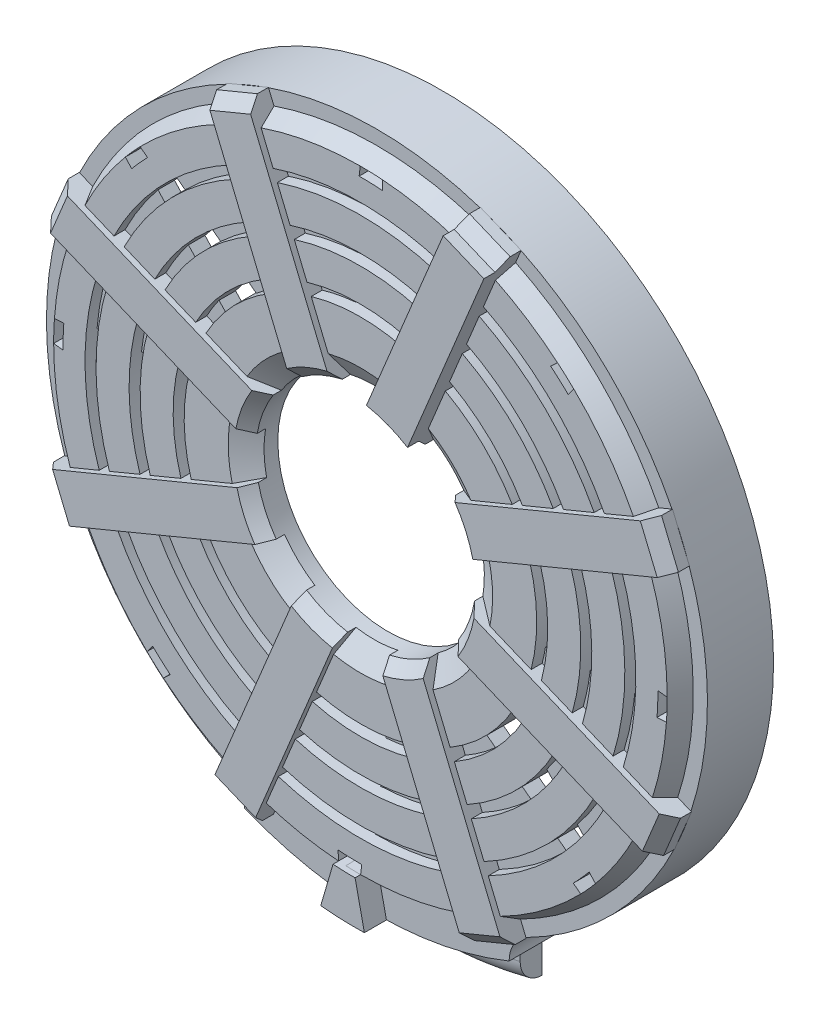
SolidWorks part; units mm, degrees
material "AISI 304"
ref_plane "Front Plane" through (0, 0, 0) normal (0, 0, 1) x (1, 0, 0)
ref_plane "Top Plane" through (0, 0, 0) normal (0, 1, 0) x (1, 0, 0)
ref_plane "Right Plane" through (0, 0, 0) normal (1, 0, 0) x (0, 0, -1)
sketch "草图2" plane through (0, 0, 20) normal (0, 0, 1) x (1, 0, 0)
  line L2 (12, -35.4955) -> (12, -29.3939)
  line L3 (-12, -29.3939) -> (-12, -35.4955)
  circle A1 centre (0, 0) radius 26.9356
  arc A2 (13.6364, -26.7217) -> (-13.6364, -26.7217) centre (0, 0) ccw
  arc A5 (13.6364, -26.7217) -> (12, -29.3939) centre (15, -29.3939) ccw
  arc A6 (-12, -35.4955) -> (12, -35.4955) centre (0, 0) ccw
  arc A7 (-12, -29.3939) -> (-13.6364, -26.7217) centre (-15, -29.3939) ccw
extrude "凸台-拉伸1" add sketch "草图2" along normal blind 2
sketch "草图3" plane through (0, 0, 22) normal (0, 0, 1) x (1, 0, 0)
  line L0 (-9, -36.3721) -> (-9, -28.6182)
  line L1 (0, -37.469) -> (0, -24.2396) construction
  line L2 (9, -36.3721) -> (9, -28.6182)
  line L3 (12, -35.4955) -> (12, -29.3939) construction
  line L4 (-12, -29.3939) -> (-12, -35.4955) construction
  line L5 (12, -35.4955) -> (12, -29.3939)
  line L6 (-12, -29.3939) -> (-12, -35.4955)
  arc A0 (-12, -35.4955) -> (12, -35.4955) centre (0, 0) ccw construction
  circle A1 centre (0, 0) radius 30 construction
  arc A2 (-13.6364, -26.7217) -> (-9, -28.6182) centre (0, 0) ccw
  arc A4 (13.6364, -26.7217) -> (12, -29.3939) centre (15, -29.3939) ccw construction
  arc A5 (-12, -29.3939) -> (-13.6364, -26.7217) centre (-15, -29.3939) ccw construction
  arc A6 (13.6364, -26.7217) -> (12, -29.3939) centre (15, -29.3939) ccw
  arc A7 (-12, -35.4955) -> (-9, -36.3721) centre (0, 0) ccw
  arc A8 (-12, -29.3939) -> (-13.6364, -26.7217) centre (-15, -29.3939) ccw
  arc A9 (9, -28.6182) -> (13.6364, -26.7217) centre (0, 0) ccw
  arc A10 (9, -36.3721) -> (12, -35.4955) centre (0, 0) ccw
  dimension "D1" = 9
extrude "切除-拉伸3" cut sketch "草图3" against normal blind 2
sketch "草图4" plane through (0, 0, 22) normal (0, 0, 1) x (1, 0, 0)
  line L0 (9, -28.6182) -> (9, -36.3721) construction
  line L1 (-9, -36.3721) -> (-9, -28.6182) construction
  line L6 (9, -35) -> (9, -36.3721)
  line L7 (-9, -36.3721) -> (-9, -35)
  arc A0 (-9, -36.3721) -> (9, -36.3721) centre (0, 0) ccw construction
  arc A1 (-9, -36.3721) -> (9, -36.3721) centre (0, 0) ccw
  arc A5 (-9, -35) -> (9, -35) centre (0, 0) ccw
extrude "切除-拉伸4" cut sketch "草图4" against normal blind 2
fillet "圆角2" radius 2 1 edges at (0, -36.1386, 22)
sketch "草图7" plane through (0, 0, 22) normal (0, 0, 1) x (1, 0, 0)
  line L2 (-9, -28.6182) -> (-9, -32.9309)
  line L3 (9, -32.9309) -> (9, -28.6182)
  line L4 (-9, -30.4467) -> (-9, -32.9309)
  line L5 (9, -32.9309) -> (9, -30.4467)
  arc A0 (-12, -29.3939) -> (-13.6364, -26.7217) centre (-15, -29.3939) ccw construction
  arc A2 (-9, -32.9309) -> (9, -32.9309) centre (0, 0) ccw
  arc A3 (9, -28.6182) -> (-9, -28.6182) centre (0, 0) ccw
  arc A4 (-9, -32.9309) -> (9, -32.9309) centre (0, 0) ccw
  arc A5 (9, -28.6182) -> (13.6364, -26.7217) centre (0, 0) ccw
  arc A6 (13.6364, -26.7217) -> (12, -29.3939) centre (15, -29.3939) ccw construction
  arc A7 (13.6364, -26.7217) -> (12, -29.3939) centre (15, -29.3939) ccw
  arc A8 (9, -28.6182) -> (-9, -28.6182) centre (0, 0) ccw construction
  arc A9 (9, -28.6182) -> (13.6364, -26.7217) centre (0, 0) ccw
  arc A10 (13.6364, -26.7217) -> (12, -29.3939) centre (15, -29.3939) ccw
  arc A11 (-12, -29.3939) -> (-13.6364, -26.7217) centre (-15, -29.3939) ccw
  arc A12 (-12, -29.3939) -> (12, -29.3939) centre (0, 0) ccw
  arc A13 (-13.6364, -26.7217) -> (13.6364, -26.7217) centre (0, 0) ccw
  arc A14 (-13.6364, -26.7217) -> (-9, -28.6182) centre (0, 0) ccw
  arc A15 (-13.6364, -26.7217) -> (-9, -28.6182) centre (0, 0) ccw
  line M7 (-9, -28.6182) -> (-9, -32.9309)
  line M9 (9, -32.9309) -> (9, -28.6182)
  arc M10 (9, -28.6182) -> (-9, -28.6182) centre (0, 0) ccw
  dimension "D1" = 0
extrude "凸台-拉伸2" add sketch "草图7" against normal blind 2 contours A11 A12 M7 M10 | A13 A12 M7 M9 | A12 A7 M9 M10 region at (0, -30.4259, 22) region at (-10.6878, -28.8911, 22) region at (10.6878, -28.8911, 22)
sketch "草图8" plane through (0, 0, 22) normal (0, 0, 1) x (1, 0, 0)
  arc A0 (-12, -29.3939) -> (12, -29.3939) centre (0, 0) ccw
  arc A1 (13.6364, -26.7217) -> (12, -29.3939) centre (15, -29.3939) ccw construction
  circle A2 centre (0, 0) radius 30 construction
  arc A3 (-12, -29.3939) -> (-13.6364, -26.7217) centre (-15, -29.3939) ccw construction
  arc A4 (13.6364, -26.7217) -> (12, -29.3939) centre (15, -29.3939) ccw
  arc A5 (-13.6364, -26.7217) -> (13.6364, -26.7217) centre (0, 0) ccw
  arc A6 (-12, -29.3939) -> (-13.6364, -26.7217) centre (-15, -29.3939) ccw
extrude "凸台-拉伸3" add sketch "草图8" along normal blind 4
sketch "草图9" plane through (0, 0, 22) normal (0, 0, 1) x (1, 0, 0)
  circle A3 centre (0, 0) radius 27
  circle A4 centre (0, 0) radius 30
extrude "凸台-拉伸5" add sketch "草图9" along normal blind 4
sketch "草图10" plane through (0, 0, 26) normal (0, 0, 1) x (1, 0, 0)
  circle A0 centre (0, 0) radius 29
extrude "凸台-拉伸6" add sketch "草图10" along normal up to surface (1.5 mm away)
chamfer "倒角1" distance 2 angle 30 1 edges at (29, 0, 27.5) first distance on face at (29, 0, 26)
sketch "草图12" plane through (0, 0, 27.5) normal (0, 0, 1) x (1, 0, 0)
  circle A0 centre (0, 0) radius 10
extrude "切除-拉伸5" cut sketch "草图12" against normal blind 18
sketch "草图13" plane through (0, 0, 20) normal (0, 0, -1) x (-1, 0, 0)
  circle A0 centre (0, 0) radius 27
extrude "凸台-拉伸7" add sketch "草图13" against normal up to surface (6 mm away) up to face at (10, 0, 26)
sketch "草图14" plane through (0, 0, 27.5) normal (0, 0, 1) x (1, 0, 0)
  circle A0 centre (0, 0) radius 10
extrude "切除-拉伸6" cut sketch "草图14" against normal blind 8
sketch "草图16" plane through (0, 0, 20) normal (0, 0, -1) x (-1, 0, 0)
  circle A0 centre (0, 0) radius 27
extrude "切除-拉伸7" cut sketch "草图16" against normal blind 5
chamfer "倒角2" distance 2 angle 32 1 edges at (10, 0, 27.5) first distance on face at (10, 0, 27.5)
sketch "草图17" plane through (0, 0, 27.5) normal (0, 0, 1) x (1, 0, 0)
  circle A0 centre (0, 0) radius 25
  circle A1 centre (0, 0) radius 24
  circle A2 centre (0, 0) radius 21
  circle A3 centre (0, 0) radius 20
  circle A4 centre (0, 0) radius 17
  circle A5 centre (0, 0) radius 16
  dimension "D1" = 50
  dimension "D2" = 48
  dimension "D3" = 42
  dimension "D4" = 40
  dimension "D5" = 34
  dimension "D6" = 32
extrude "切除-拉伸10" cut sketch "草图17" against normal blind 1 contours A0 A1 | A2 A3 | A4 A5 region at (-24.2929, 0, 27.5) region at (-20.406, 0, 27.5) region at (-16.5192, 0, 27.5)
sketch "草图18" plane through (0, 0, 0) normal (0, 1, 0) x (1, 0, 0)
  line L0 (0, -20) -> (0, -40.9012) construction
  line L1 (-10.5, -23.7655) -> (-7.5, -23.7655)
  line L2 (-10.5, -23.7655) -> (-10.5, -22.7655)
  line L3 (-4.5, -23.7655) -> (-1.5, -23.7655)
  line L4 (-4.5, -23.7655) -> (-4.5, -22.7655)
  line L5 (-4.5, -22.7655) -> (-1.5, -22.7655)
  line L6 (-1.5, -23.7655) -> (-1.5, -22.7655)
  line L7 (-10.5, -22.7655) -> (-7.5, -22.7655)
  line L8 (-7.5, -23.7655) -> (-7.5, -22.7655)
  line L9 (7.5, -23.7655) -> (7.5, -22.7655)
  line L10 (10.5, -22.7655) -> (7.5, -22.7655)
  line L11 (1.5, -23.7655) -> (1.5, -22.7655)
  line L12 (4.5, -22.7655) -> (1.5, -22.7655)
  line L13 (4.5, -23.7655) -> (4.5, -22.7655)
  line L14 (4.5, -23.7655) -> (1.5, -23.7655)
  line L15 (10.5, -23.7655) -> (10.5, -22.7655)
  line L16 (10.5, -23.7655) -> (7.5, -23.7655)
  dimension "D1" = 1.5
  dimension "D2" = 2
extrude "切除-拉伸11" cut sketch "草图18" against normal blind 71
sketch "草图25" plane through (0, 0, 25) normal (0, 0, -1) x (-1, 0, 0)
  circle A0 centre (0, 0) radius 10.0206
  circle A1 centre (0, 0) radius 10.8
extrude "凸台-拉伸18" add sketch "草图25" against normal blind 1
sketch "草图26" plane through (0, 0, 27.5) normal (0, 0, 1) x (1, 0, 0)
  line L0 (0, 0.2463) -> (48.6925, 0.2463) construction
  line L1 (0, 0) -> (0, 32.9764) construction
  line L3 (8.1431, 5.8044) -> (26.8317, 13.5455)
  line L5 (9.7667, 2.1473) -> (28.3624, 9.8499)
  line L6 (26.8317, 13.5455) -> (28.3624, 9.8499)
  line L7 (9.8623, -1.6537) -> (28.551, -9.3948)
  line L8 (28.551, -9.3948) -> (27.0202, -13.0903)
  line L9 (8.4245, -5.3877) -> (27.0202, -13.0903)
  line L11 (5.8044, -8.1431) -> (13.5455, -26.8317)
  line L12 (13.5455, -26.8317) -> (9.8499, -28.3624)
  line L13 (2.1473, -9.7667) -> (9.8499, -28.3624)
  line L15 (-1.6537, -9.8623) -> (-9.3948, -28.551)
  line L16 (-9.3948, -28.551) -> (-13.0903, -27.0202)
  line L17 (-5.3877, -8.4245) -> (-13.0903, -27.0202)
  line L19 (-8.1431, -5.8044) -> (-26.8317, -13.5455)
  line L20 (-26.8317, -13.5455) -> (-28.3624, -9.8499)
  line L21 (-9.7667, -2.1473) -> (-28.3624, -9.8499)
  line L23 (-9.8623, 1.6537) -> (-28.551, 9.3948)
  line L24 (-28.551, 9.3948) -> (-27.0202, 13.0903)
  line L25 (-8.4245, 5.3877) -> (-27.0202, 13.0903)
  line L27 (-5.8044, 8.1431) -> (-13.5455, 26.8317)
  line L28 (-13.5455, 26.8317) -> (-9.8499, 28.3624)
  line L29 (-2.1473, 9.7667) -> (-9.8499, 28.3624)
  line L31 (1.6537, 9.8623) -> (9.3948, 28.551)
  line L32 (9.3948, 28.551) -> (13.0903, 27.0202)
  line L33 (5.3877, 8.4245) -> (13.0903, 27.0202)
  circle A0 centre (0, 0) radius 10
  point P43 (0, 0)
  circle M36 centre (0, 0) radius 25
  circle M37 centre (0, 0) radius 27.8453
  dimension "D1" = 8
extrude "凸台-拉伸19" add sketch "草图26" along normal mid plane 3 contours L29 L28 L27 M37 | A0 L29 L27 M36 | L29 L27 M36 M37 | L33 L32 L31 M37 | L33 L31 M36 M37 | A0 L33 L31 M36 | A0 L5 L3 M36 | L5 L3 M36 M37 | L6 L3 L5 M37 | L9 L7 M36 M37 | L9 L8 L7 M37 | A0 L9 L7 M36 | A0 L13 L11 M36 | L13 L11 M36 M37 | L13 L12 L11 M37 | L17 L16 L15 M37 | A0 L17 L15 M36 | L17 L15 M36 M37 | A0 L21 L19 M36 | L21 L19 M36 M37 | L21 L20 L19 M37 | A0 L25 L23 M36 | L25 L23 M36 M37 | L25 L24 L23 M37 region at (16.0277, 6.907, 27.5) region at (24.2924, 10.3294, 27.5) region at (6.4493, 16.2172, 27.5) region at (26.6005, 11.2908, 27.5) region at (9.8734, 24.4813, 27.5) region at (10.8255, 26.7932, 27.5) region at (16.2172, -6.4493, 27.5) region at (-6.907, 16.0277, 27.5) region at (24.4813, -9.8734, 27.5) region at (-10.3294, 24.2924, 27.5) region at (26.7932, -10.8255, 27.5) region at (-11.2908, 26.6005, 27.5) region at (6.907, -16.0277, 27.5) region at (-16.2172, 6.4493, 27.5) region at (10.3294, -24.2924, 27.5) region at (-24.4813, 9.8734, 27.5) region at (11.2908, -26.6005, 27.5) region at (-26.7932, 10.8255, 27.5) region at (-6.4493, -16.2172, 27.5) region at (-16.0277, -6.907, 27.5) region at (-9.8734, -24.4813, 27.5) region at (-24.2924, -10.3294, 27.5) region at (-10.8255, -26.7932, 27.5) region at (-26.6005, -11.2908, 27.5)
chamfer "倒角3" distance 2 angle 45 8 edges at (4.0579, -9.1397, 29) (-3.5934, -9.3321, 29) (-9.1397, -4.0579, 29) (-9.3321, 3.5934, 29) (-4.0579, 9.1397, 29) (3.5934, 9.3321, 29) (9.1397, 4.0579, 29) (9.3321, -3.5934, 29)
chamfer "倒角4" distance 2 angle 45 8 edges at (11.2426, 27.7856, 29) (27.5971, 11.6977, 29) (27.7856, -11.2426, 29) (11.6977, -27.5971, 29) (-11.2426, -27.7856, 29) (-11.6977, 27.5971, 29) (-27.5971, -11.6977, 29) (-27.7856, 11.2426, 29)
sketch "草图30" plane through (0, 0, 27.5) normal (0, 0, 1) x (1, 0, 0)
  line L0 (-11.2426, -27.7856) -> (11.2426, 27.7856) construction
  line L1 (-2.1261, -24.9094) -> (-2.1754, -23.9012)
  line L2 (-12.8439, -16.6143) -> (-12.1044, -15.9212)
  line L3 (-27.7856, 11.2426) -> (27.7856, -11.2426) construction
  line L4 (0.3579, -24.9974) -> (0.4784, -23.9952)
  line L5 (-15.1955, -14.4947) -> (-14.5827, -13.6874)
  line L6 (2.1261, 24.9094) -> (2.1754, 23.9012)
  line L7 (-2.5653, -15.9192) -> (-2.5715, -15.792)
  line L8 (-1.9862, -27.7744) -> (-2.0277, -26.9237)
  line L9 (0.0156, -27.8453) -> (0.1172, -26.9997)
  line L10 (1.4322, -16.0608) -> (1.4474, -15.9344)
  line L11 (-2.5217, -16.8119) -> (-2.5653, -15.9192)
  line L12 (-12.7382, -11.2578) -> (-12.1977, -10.5459)
  line L13 (1.3255, -16.9482) -> (1.4322, -16.0608)
  line L14 (0.8405, -20.9832) -> (0.9615, -19.9769)
  line L15 (-9.8787, -13.8351) -> (-9.2265, -13.2239)
  line L16 (-2.3234, -20.8711) -> (-2.3728, -19.8587)
  line L17 (-12.1977, -10.5459) -> (-12.1208, -10.4445)
  line L18 (-19.3745, -19.9997) -> (-18.8596, -19.3214)
  line L19 (-17.8867, -21.3408) -> (-17.2653, -20.7584)
  line L20 (-9.2265, -13.2239) -> (-9.1336, -13.1368)
  line L21 (-0.3579, 24.9974) -> (-0.4784, 23.9952)
  line L22 (-17.6402, -17.7151) -> (-17.0298, -16.9111)
  line L23 (-15.7938, -19.3792) -> (-15.0574, -18.6889)
  line L24 (2.5653, 15.9192) -> (2.5715, 15.792)
  line L25 (1.9862, 27.7744) -> (2.0277, 26.9237)
  line L26 (-0.0156, 27.8453) -> (-0.1172, 26.9997)
  line L27 (-1.4322, 16.0608) -> (-1.4474, 15.9344)
  line L28 (12.8439, 16.6143) -> (12.1044, 15.9212)
  line L29 (2.5217, 16.8119) -> (2.5653, 15.9192)
  line L30 (15.1955, 14.4947) -> (14.5827, 13.6874)
  line L31 (12.7382, 11.2578) -> (12.1977, 10.5459)
  line L32 (-1.3255, 16.9482) -> (-1.4322, 16.0608)
  line L33 (9.8787, 13.8351) -> (9.2265, 13.2239)
  line L34 (12.1977, 10.5459) -> (12.1208, 10.4445)
  line L35 (19.3745, 19.9997) -> (18.8596, 19.3214)
  line L36 (17.8867, 21.3408) -> (17.2653, 20.7584)
  line L37 (9.2265, 13.2239) -> (9.1336, 13.1368)
  line L38 (-0.8405, 20.9832) -> (-0.9615, 19.9769)
  line L39 (17.6402, 17.7151) -> (17.0298, 16.9111)
  line L40 (2.3234, 20.8711) -> (2.3728, 19.8587)
  line L41 (15.7938, 19.3792) -> (15.0574, 18.6889)
  arc A0 (-8.5459, -26.5015) -> (9.0146, -26.3457) centre (0, 0) ccw construction
  arc A1 (-1.9862, -27.7744) -> (0.0156, -27.8453) centre (0, 0) ccw
  arc A2 (-3.987, -15.4953) -> (4.4659, -15.3641) centre (0, 0) ccw construction
  arc A3 (-2.5715, -15.792) -> (1.4474, -15.9344) centre (0, 0) ccw
  arc A4 (-7.4531, -23.8632) -> (7.9233, -23.7112) centre (0, 0) ccw construction
  arc A5 (-4.3732, -16.4279) -> (4.8507, -16.2933) centre (0, 0) ccw construction
  arc A6 (-7.0688, -22.9354) -> (7.5397, -22.7849) centre (0, 0) ccw construction
  arc A7 (-5.9149, -20.1498) -> (6.3881, -20.0048) centre (0, 0) ccw construction
  arc A8 (-5.5299, -19.2203) -> (6.004, -19.0775) centre (0, 0) ccw construction
  arc A9 (-2.1261, -24.9094) -> (0.3579, -24.9974) centre (0, 0) ccw
  arc A10 (-2.5217, -16.8119) -> (1.3255, -16.9482) centre (0, 0) ccw
  arc A11 (-2.1754, -23.9012) -> (0.4784, -23.9952) centre (0, 0) ccw
  arc A12 (-2.3234, -20.8711) -> (0.8405, -20.9832) centre (0, 0) ccw
  arc A13 (-2.3728, -19.8587) -> (0.9615, -19.9769) centre (0, 0) ccw
  arc A14 (-2.0277, -26.9237) -> (0.1172, -26.9997) centre (0, 0) ccw
  arc A15 (-17.2653, -20.7584) -> (-18.8596, -19.3214) centre (0, 0) cw
  arc A16 (-12.1044, -15.9212) -> (-14.5827, -13.6874) centre (0, 0) cw
  arc A17 (-12.8439, -16.6143) -> (-15.1955, -14.4947) centre (0, 0) cw
  arc A18 (-15.0574, -18.6889) -> (-17.0298, -16.9111) centre (0, 0) cw
  arc A19 (-9.8787, -13.8351) -> (-12.7382, -11.2578) centre (0, 0) cw
  arc A20 (-15.7938, -19.3792) -> (-17.6402, -17.7151) centre (0, 0) cw
  arc A21 (-9.1336, -13.1368) -> (-12.1208, -10.4445) centre (0, 0) cw
  arc A22 (-17.8867, -21.3408) -> (-19.3745, -19.9997) centre (0, 0) cw
  arc A23 (1.9862, 27.7744) -> (-0.0156, 27.8453) centre (0, 0) ccw
  arc A24 (2.5715, 15.792) -> (-1.4474, 15.9344) centre (0, 0) ccw
  arc A25 (2.1261, 24.9094) -> (-0.3579, 24.9974) centre (0, 0) ccw
  arc A26 (2.5217, 16.8119) -> (-1.3255, 16.9482) centre (0, 0) ccw
  arc A27 (2.1754, 23.9012) -> (-0.4784, 23.9952) centre (0, 0) ccw
  arc A28 (2.3234, 20.8711) -> (-0.8405, 20.9832) centre (0, 0) ccw
  arc A29 (2.3728, 19.8587) -> (-0.9615, 19.9769) centre (0, 0) ccw
  arc A30 (2.0277, 26.9237) -> (-0.1172, 26.9997) centre (0, 0) ccw
  arc A31 (17.2653, 20.7584) -> (18.8596, 19.3214) centre (0, 0) cw
  arc A32 (12.1044, 15.9212) -> (14.5827, 13.6874) centre (0, 0) cw
  arc A33 (12.8439, 16.6143) -> (15.1955, 14.4947) centre (0, 0) cw
  arc A34 (15.0574, 18.6889) -> (17.0298, 16.9111) centre (0, 0) cw
  arc A35 (9.8787, 13.8351) -> (12.7382, 11.2578) centre (0, 0) cw
  arc A36 (15.7938, 19.3792) -> (17.6402, 17.7151) centre (0, 0) cw
  arc A37 (9.1336, 13.1368) -> (12.1208, 10.4445) centre (0, 0) cw
  arc A38 (17.8867, 21.3408) -> (19.3745, 19.9997) centre (0, 0) cw
  point P13 (-0.9859, -27.8278)
  point P14 (-0.5665, -15.99)
  point P67 (-10.7121, -11.8849)
  point P68 (-18.6427, -20.6836)
  point P104 (0.9859, 27.8278)
  point P105 (0.5665, 15.99)
  point P106 (10.7121, 11.8849)
  point P107 (18.6427, 20.6836)
extrude "切除-拉伸13" cut sketch "草图30" against normal blind 10
sketch "草图31" plane through (0, 0, 27.5) normal (0, 0, 1) x (1, 0, 0)
  line L0 (27.7856, -11.2426) -> (-27.7856, 11.2426) construction
  line L1 (19.3215, -18.8595) -> (19.9997, -19.3745)
  line L2 (15.8985, -2.5645) -> (16.8122, -2.52)
  line L3 (11.2426, 27.7856) -> (-11.2426, -27.7856) construction
  line L4 (15.8985, -2.5645) -> (15.7923, -2.5697)
  line L5 (16.0402, 1.433) -> (16.9484, 1.3239)
  line L6 (16.0402, 1.433) -> (15.9346, 1.4456)
  line L7 (19.8589, -2.3717) -> (20.8712, -2.3224)
  line L8 (20.7583, -17.2654) -> (21.3408, -17.8867)
  line L9 (19.9769, 0.9603) -> (20.9832, 0.8395)
  line L10 (23.9952, 0.4778) -> (24.9974, 0.3575)
  line L11 (18.6886, -15.0578) -> (19.379, -15.7942)
  line L12 (23.9013, -2.1748) -> (24.9095, -2.1257)
  line L13 (26.9238, -2.0276) -> (27.7744, -1.9862)
  line L14 (16.9115, -17.0294) -> (17.7154, -17.6399)
  line L15 (26.9997, 0.1171) -> (27.8453, 0.0156)
  line L16 (13.6883, -14.5819) -> (14.4955, -15.1948)
  line L17 (15.9205, -12.1053) -> (16.6137, -12.8447)
  line L18 (10.5305, -12.1839) -> (10.4458, -12.1196)
  line L19 (10.5305, -12.1839) -> (11.259, -12.7371)
  line L20 (13.2086, -9.2127) -> (13.1358, -9.1351)
  line L21 (13.2086, -9.2127) -> (13.8342, -9.88)
  line L22 (-15.8985, 2.5645) -> (-16.8122, 2.52)
  line L23 (-15.8985, 2.5645) -> (-15.7923, 2.5697)
  line L24 (-16.0402, -1.433) -> (-16.9484, -1.3239)
  line L25 (-16.0402, -1.433) -> (-15.9346, -1.4456)
  line L26 (-19.8589, 2.3717) -> (-20.8712, 2.3224)
  line L27 (-19.9769, -0.9603) -> (-20.9832, -0.8395)
  line L28 (-23.9952, -0.4778) -> (-24.9974, -0.3575)
  line L29 (-23.9013, 2.1748) -> (-24.9095, 2.1257)
  line L30 (-26.9238, 2.0276) -> (-27.7744, 1.9862)
  line L31 (-26.9997, -0.1171) -> (-27.8453, -0.0156)
  line L32 (-19.3215, 18.8595) -> (-19.9997, 19.3745)
  line L33 (-20.7583, 17.2654) -> (-21.3408, 17.8867)
  line L34 (-18.6886, 15.0578) -> (-19.379, 15.7942)
  line L35 (-16.9115, 17.0294) -> (-17.7154, 17.6399)
  line L36 (-13.6883, 14.5819) -> (-14.4955, 15.1948)
  line L37 (-15.9205, 12.1053) -> (-16.6137, 12.8447)
  line L38 (-10.5305, 12.1839) -> (-10.4458, 12.1196)
  line L39 (-10.5305, 12.1839) -> (-11.259, 12.7371)
  line L40 (-13.2086, 9.2127) -> (-13.1358, 9.1351)
  line L41 (-13.2086, 9.2127) -> (-13.8342, 9.88)
  arc A0 (26.9238, -2.0276) -> (26.9997, 0.1171) centre (0, 0) ccw
  arc A1 (26.5015, -8.5459) -> (26.3457, 9.0146) centre (0, 0) ccw construction
  arc A2 (27.7744, -1.9862) -> (27.8453, 0.0156) centre (0, 0) ccw
  arc A3 (15.4953, -3.987) -> (15.3641, 4.4659) centre (0, 0) ccw construction
  arc A4 (15.7923, -2.5697) -> (15.9346, 1.4456) centre (0, 0) ccw
  arc A5 (23.8632, -7.4531) -> (23.7112, 7.9233) centre (0, 0) ccw construction
  arc A6 (22.9354, -7.0688) -> (22.7849, 7.5397) centre (0, 0) ccw construction
  arc A7 (20.1498, -5.9149) -> (20.0048, 6.3881) centre (0, 0) ccw construction
  arc A8 (19.2203, -5.5299) -> (19.0775, 6.004) centre (0, 0) ccw construction
  arc A9 (16.4279, -4.3732) -> (16.2933, 4.8507) centre (0, 0) ccw construction
  arc A10 (24.9095, -2.1257) -> (24.9974, 0.3575) centre (0, 0) ccw
  arc A11 (23.9013, -2.1748) -> (23.9952, 0.4778) centre (0, 0) ccw
  arc A12 (20.8712, -2.3224) -> (20.9832, 0.8395) centre (0, 0) ccw
  arc A13 (19.8589, -2.3717) -> (19.9769, 0.9603) centre (0, 0) ccw
  arc A14 (16.8122, -2.52) -> (16.9484, 1.3239) centre (0, 0) ccw
  arc A15 (13.8342, -9.88) -> (11.259, -12.7371) centre (0, 0) cw
  arc A16 (15.9205, -12.1053) -> (13.6883, -14.5819) centre (0, 0) cw
  arc A17 (16.6137, -12.8447) -> (14.4955, -15.1948) centre (0, 0) cw
  arc A18 (18.6886, -15.0578) -> (16.9115, -17.0294) centre (0, 0) cw
  arc A19 (19.379, -15.7942) -> (17.7154, -17.6399) centre (0, 0) cw
  arc A20 (13.1358, -9.1351) -> (10.4458, -12.1196) centre (0, 0) cw
  arc A21 (21.3408, -17.8867) -> (19.9997, -19.3745) centre (0, 0) cw
  arc A22 (20.7583, -17.2654) -> (19.3215, -18.8595) centre (0, 0) cw
  arc A23 (-26.9238, 2.0276) -> (-26.9997, -0.1171) centre (0, 0) ccw
  arc A24 (-27.7744, 1.9862) -> (-27.8453, -0.0156) centre (0, 0) ccw
  arc A25 (-15.7923, 2.5697) -> (-15.9346, -1.4456) centre (0, 0) ccw
  arc A26 (-24.9095, 2.1257) -> (-24.9974, -0.3575) centre (0, 0) ccw
  arc A27 (-23.9013, 2.1748) -> (-23.9952, -0.4778) centre (0, 0) ccw
  arc A28 (-20.8712, 2.3224) -> (-20.9832, -0.8395) centre (0, 0) ccw
  arc A29 (-19.8589, 2.3717) -> (-19.9769, -0.9603) centre (0, 0) ccw
  arc A30 (-16.8122, 2.52) -> (-16.9484, -1.3239) centre (0, 0) ccw
  arc A31 (-13.8342, 9.88) -> (-11.259, 12.7371) centre (0, 0) cw
  arc A32 (-15.9205, 12.1053) -> (-13.6883, 14.5819) centre (0, 0) cw
  arc A33 (-16.6137, 12.8447) -> (-14.4955, 15.1948) centre (0, 0) cw
  arc A34 (-18.6886, 15.0578) -> (-16.9115, 17.0294) centre (0, 0) cw
  arc A35 (-19.379, 15.7942) -> (-17.7154, 17.6399) centre (0, 0) cw
  arc A36 (-13.1358, 9.1351) -> (-10.4458, 12.1196) centre (0, 0) cw
  arc A37 (-21.3408, 17.8867) -> (-19.9997, 19.3745) centre (0, 0) cw
  arc A38 (-20.7583, 17.2654) -> (-19.3215, 18.8595) centre (0, 0) cw
  point P11 (27.8278, -0.9859)
  point P15 (15.9694, -0.5658)
  point P65 (11.8696, -10.6983)
  point P66 (20.6836, -18.6427)
  point P85 (-27.8278, 0.9859)
  point P86 (-15.9694, 0.5658)
  point P105 (-11.8696, 10.6983)
  point P106 (-20.6836, 18.6427)
extrude "切除-拉伸14" cut sketch "草图31" against normal blind 10
sketch "草图32" plane through (0, 0, 26) normal (0, 0, 1) x (1, 0, 0)
  line L0 (-0.9859, -27.8278) -> (0, 0) construction
  line L2 (-1.9862, -27.7744) -> (-3.1049, -31.5968)
  line L3 (0.0156, -27.8453) -> (0.861, -31.7373)
  arc A1 (-1.9862, -27.7744) -> (0.0156, -27.8453) centre (0, 0) ccw construction
  arc A2 (-9, -30.4467) -> (9, -30.4467) centre (0, 0) ccw construction
  arc A3 (-1.9862, -27.7744) -> (0.0156, -27.8453) centre (0, 0) ccw
  arc A4 (-3.1049, -31.5968) -> (0.861, -31.7373) centre (0, 0) ccw
  point P9 (-1.1242, -31.7291)
  point P13 (-1.1242, -31.7291)
extrude "凸台-拉伸20" add sketch "草图32" along normal blind 3 separate body
sketch "草图34" plane through (0, 0, 29) normal (0, 0, 1) x (1, 0, 0)
  circle A0 centre (0, 0) radius 44.8882
extrude "切除-拉伸15" cut sketch "草图34" against normal blind 1
sketch "草图35" plane through (0, 0, 28) normal (0, 0, 1) x (1, 0, 0)
  line L2 (5.7759, 9.3616) -> (12.7076, 26.0964)
  line L3 (5.7759, 9.3616) -> (12.7076, 26.0964)
  line L7 (12.7076, 26.0964) -> (9.0121, 27.6271)
  line L8 (12.7076, 26.0964) -> (9.0121, 27.6271)
  line L9 (9.0121, 27.6271) -> (2.0455, 10.8081)
  line L10 (9.0121, 27.6271) -> (2.0455, 10.8081)
  arc A1 (5.7759, 9.3616) -> (2.0455, 10.8081) centre (0, 0) ccw
  arc A2 (5.7759, 9.3616) -> (2.0455, 10.8081) centre (0, 0) ccw
  dimension "D1" = 0
extrude "凸台-拉伸21" add sketch "草图35" along normal blind 1
